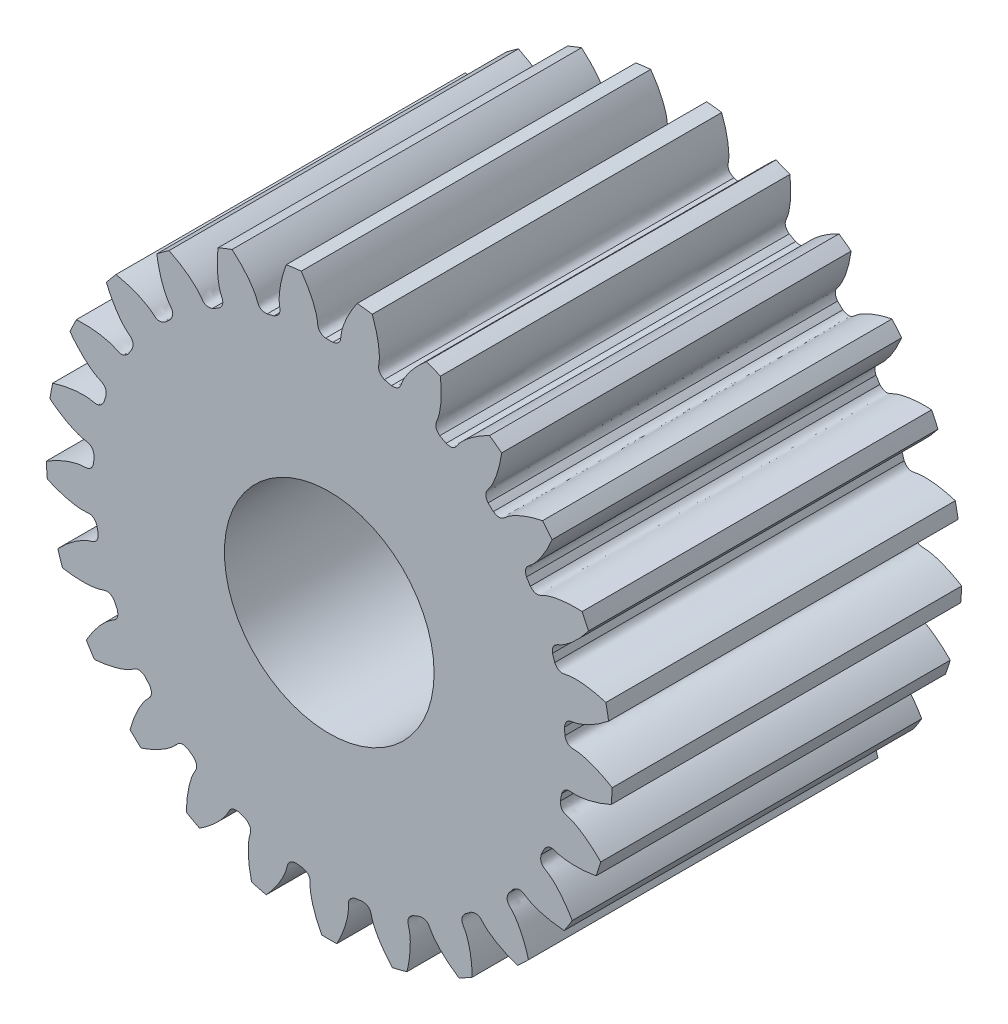
SolidWorks part; units mm, degrees
ref_plane "前视基准面" through (0, 0, 0) normal (0, 0, 1) x (1, 0, 0)
ref_plane "上视基准面" through (0, 0, 0) normal (0, 1, 0) x (1, 0, 0)
ref_plane "右视基准面" through (0, 0, 0) normal (1, 0, 0) x (0, 0, -1)
sketch "草图1" plane through (0, 0, 0) normal (0, 0, 1) x (1, 0, 0)
  circle A0 centre (0, 0) radius 4.05
extrude "凸台-拉伸1" add sketch "草图1" along normal blind 5
ref_axis "基准轴1" through (0, 0, 5) along (0, 0, -1)
sketch "草图2" plane through (0, 0, 0) normal (0, 0, 1) x (1, 0, 0)
  line L0 (0, 0) -> (0, 4.05) construction
  circle A0 centre (0, 0) radius 4.05 construction
  arc A1 (0.0516, 3.3746) -> (-0.0516, 3.3746) centre (0, 0) ccw
  arc A2 (0.9616, 4.5945) -> (-0.9616, 4.5945) centre (0, 0) ccw
  spline S0 degree 3 poles (0.0516, 3.3746) (0.172, 3.4005) (0.1607, 3.4732) (0.1723, 3.5454) (0.1739, 3.5544) (0.176, 3.5648) (0.1786, 3.5765) (0.1817, 3.5895) (0.1855, 3.6038) (0.19, 3.6194) (0.1952, 3.6362) (0.2011, 3.6543) (0.2079, 3.6736) (0.2156, 3.6941) (0.2241, 3.7157) (0.2337, 3.7384) (0.2443, 3.7622) (0.256, 3.7871) (0.2687, 3.813) (0.2827, 3.84) (0.2978, 3.8678) (0.3143, 3.8966) (0.332, 3.9262) (0.351, 3.9567) (0.3714, 3.988) (0.3932, 4.0201) (0.4165, 4.0528) (0.4413, 4.0862) (0.4676, 4.1202) (0.4954, 4.1548) (0.5249, 4.1899) (0.556, 4.2254) (0.5887, 4.2614) (0.6231, 4.2978) (0.6592, 4.3344) (0.6971, 4.3713) (0.7367, 4.4084) (0.7781, 4.4456) (0.8212, 4.483) (0.882, 4.5334) (0.9292, 4.5702) (0.9616, 4.5945) knots 0 0 0 0 0.130741 0.135745 0.141658 0.148481 0.156214 0.164857 0.174409 0.184871 0.196243 0.208524 0.221715 0.235816 0.250827 0.266748 0.283578 0.301318 0.319968 0.339527 0.359996 0.381375 0.403664 0.426862 0.450971 0.475988 0.501916 0.528753 0.556501 0.585157 0.614724 0.6452 0.676587 0.708882 0.742088 0.776203 0.811228 0.847163 0.884008 0.921762 1 1 1 1
  spline S1 degree 3 poles (-0.0516, 3.3746) (-0.172, 3.4005) (-0.1607, 3.4732) (-0.1723, 3.5454) (-0.1739, 3.5544) (-0.176, 3.5648) (-0.1786, 3.5765) (-0.1817, 3.5895) (-0.1855, 3.6038) (-0.19, 3.6194) (-0.1952, 3.6362) (-0.2011, 3.6543) (-0.2079, 3.6736) (-0.2156, 3.6941) (-0.2241, 3.7157) (-0.2337, 3.7384) (-0.2443, 3.7622) (-0.256, 3.7871) (-0.2687, 3.813) (-0.2827, 3.84) (-0.2978, 3.8678) (-0.3143, 3.8966) (-0.332, 3.9262) (-0.351, 3.9567) (-0.3714, 3.988) (-0.3932, 4.0201) (-0.4165, 4.0528) (-0.4413, 4.0862) (-0.4676, 4.1202) (-0.4954, 4.1548) (-0.5249, 4.1899) (-0.556, 4.2254) (-0.5887, 4.2614) (-0.6231, 4.2978) (-0.6592, 4.3344) (-0.6971, 4.3713) (-0.7367, 4.4084) (-0.7781, 4.4456) (-0.8212, 4.483) (-0.882, 4.5334) (-0.9292, 4.5702) (-0.9616, 4.5945) knots 0 0 0 0 0.130741 0.135745 0.141658 0.148481 0.156214 0.164857 0.174409 0.184871 0.196243 0.208524 0.221715 0.235816 0.250827 0.266748 0.283578 0.301318 0.319968 0.339527 0.359996 0.381375 0.403664 0.426862 0.450971 0.475988 0.501916 0.528753 0.556501 0.585157 0.614724 0.6452 0.676587 0.708882 0.742088 0.776203 0.811228 0.847163 0.884008 0.921762 1 1 1 1
extrude "切除-拉伸1" cut sketch "草图2" along normal through all
pattern_circular "阵列(圆周)1" count 25 every 14.4 about axis through (0, 0, 5) along (0, 0, -1) of "切除-拉伸1"
sketch "草图3" plane through (0, 0, 0) normal (0, 0, 1) x (1, 0, 0)
  circle A0 centre (0, 0) radius 3.75 construction
  dimension "Dn" = 7.5
sketch "草图4" plane through (0, 0, 0) normal (0, 0, 1) x (1, 0, 0)
  circle A0 centre (0, 0) radius 1.5
  dimension "D1" = 3
extrude "切除-拉伸3" cut sketch "草图4" along normal through all
